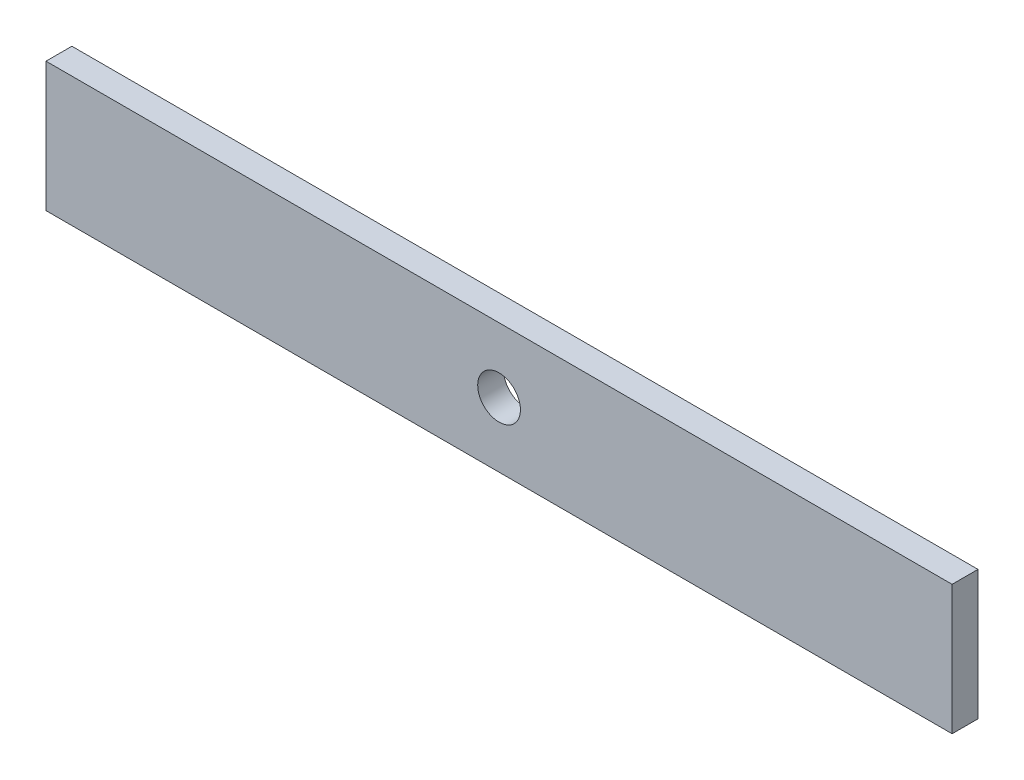
SolidWorks part; units mm, degrees
material "AISI 1020"
ref_plane "Plano frontal" through (0, 0, 0) normal (0, 0, 1) x (1, 0, 0)
ref_plane "Plano superior" through (0, 0, 0) normal (0, 1, 0) x (1, 0, 0)
ref_plane "Plano direito" through (0, 0, 0) normal (1, 0, 0) x (0, 0, -1)
sketch "Esboço1" plane through (0, 0, 0) normal (0, 0, 1) x (1, 0, 0)
  line L1 (-35, 5) -> (35, 5)
  line L2 (-35, 5) -> (-35, -5)
  line L3 (-35, -5) -> (35, -5)
  line L4 (35, 5) -> (35, -5)
  line L5 (-35, 5) -> (35, -5) construction
  line L6 (-35, -5) -> (35, 5) construction
  point P0 (0, 0)
  dimension "D1" = 70
  dimension "D2" = 10
base flange "Flange-base1" sketch "Esboço1" thickness 2 reverse thickness direction no parameters "D1"=2.7366
hole_wizard "Broca de rosquear de cano para tarraxa de 1/81" positions "Esboço7" profile "Esboço8" hole size "1/8" standard "Ansi Inch"
sketch "Esboço7" plane through (0, 0, -2) normal (0, 0, -1) x (-1, 0, 0)
  point P0 (0, 0)
sketch "Esboço8" plane through (0, 0, -2) normal (1, 0, 0) x (0, 1, 0)
  line L0 (0, 0) -> (0, 4.9914)
  line L1 (0, 4.9914) -> (1.65, 4)
  line L2 (1.65, 4) -> (1.65, 0)
  line L5 (1.65, 0) -> (0, 0)
  line L10 (0, 4.9914) -> (-1.65, 4) construction
  line L11 (0, -6.35) -> (0, 107.95) construction
  dimension "Hole Dia." = 3.3
  dimension "Hole Depth" = 4
  dimension "Drill Angle" = 118
sketch "Curva-Linhas1" [suppressed] plane through (0, 0, 0) normal (0, 1, 0) x (1, 0, 0)
sketch "Caixa delimitadora1" [suppressed] plane through (0, 0, 0) normal (0, 1, 0) x (1, 0, 0)
sheet metal parameters "Chapa metálica1" thickness 2 parameters "D1"=2.7366
flat pattern "Padrão-Plano1" [suppressed]
sketch "Curva-Linhas2" plane through (0, 0, 0) normal (0, 0, 1) x (1, 0, 0)
  line L0 (25.8562, -2.5) -> (25.8562, 2.5) construction
  line L1 (-25.8562, 2.5) -> (-25.8562, -2.5) construction
  line L2 (25.8562, -2.5) -> (25.8562, 2.5) construction
  line L3 (-25.8562, 2.5) -> (-25.8562, -2.5) construction
sketch3d "Caixa delimitadora2" [suppressed]
  line L0 (-37.5, -2.5, 0) -> (37.5, -2.5, 0) construction
  line L1 (-37.5, 2.5, 0) -> (37.5, 2.5, 0) construction
  line L2 (-37.5, -2.5, 0) -> (-37.5, 2.5, 0) construction
  line L3 (37.5, -2.5, 0) -> (37.5, 2.5, 0) construction
sheet metal parameters "Chapa metálica4" thickness 2 parameters "D1"=2.7366
flat pattern "Padrão-Plano1"
sketch "Curva-Linhas2" plane through (0, 0, 0) normal (0, 0, 1) x (1, 0, 0)
  point P0 (23.3562, -5)
  point P1 (23.3562, 5)
  point P2 (-23.3562, 5)
  point P3 (-23.3562, -5)
sketch3d "Caixa delimitadora2" [suppressed]
  line L0 (-35, -5, 0) -> (35, -5, 0) construction
  line L1 (-35, 5, 0) -> (35, 5, 0) construction
  line L2 (-35, -5, 0) -> (-35, 5, 0) construction
  line L3 (35, -5, 0) -> (35, 5, 0) construction
